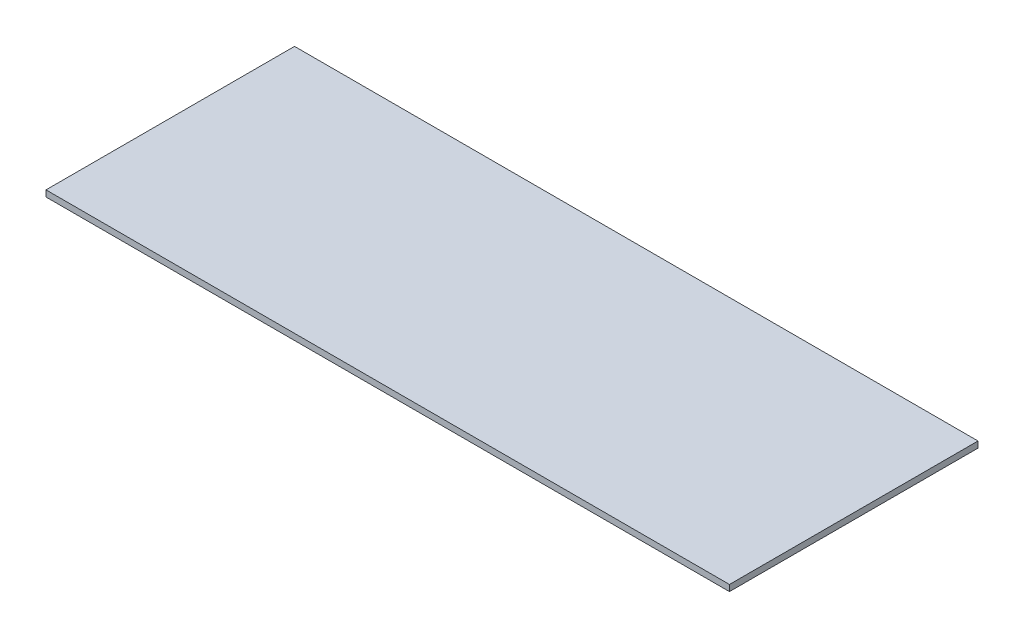
SolidWorks part; units mm, degrees
material "Acrylic (Medium-high impact)"
ref_plane "Front Plane" through (0, 0, 0) normal (0, 0, 1) x (1, 0, 0)
ref_plane "Top Plane" through (0, 0, 0) normal (0, 1, 0) x (1, 0, 0)
ref_plane "Right Plane" through (0, 0, 0) normal (1, 0, 0) x (0, 0, -1)
sketch "Sketch1" plane through (0, 0, 0) normal (0, 1, 0) x (1, 0, 0)
  line L1 (-372.6379, 124.9095) -> (325.8621, 124.9095)
  line L2 (-372.6379, 124.9095) -> (-372.6379, -129.0905)
  line L3 (-372.6379, -129.0905) -> (325.8621, -129.0905)
  line L4 (325.8621, 124.9095) -> (325.8621, -129.0905)
  line L5 (-372.6379, 124.9095) -> (325.8621, -129.0905) construction
  line L6 (-372.6379, -129.0905) -> (325.8621, 124.9095) construction
  point P4 (-23.3879, -2.0905)
  dimension "D1" = 254
  dimension "D2" = 698.5
extrude "Baseplate" add sketch "Sketch1" along normal blind 6.35
sketch "Battery Adaptors" plane through (0, 6.35, 0) normal (0, 1, 0) x (1, 0, 0)
  line L0 (238.575, -103.6905) -> (320.7821, -103.6905) construction
  line L1 (238.575, -103.6905) -> (238.575, -5.2655) construction
  line L2 (238.575, -5.2655) -> (320.7821, -5.2655) construction
  line L3 (320.7821, -103.6905) -> (320.7821, -5.2655) construction
  line L6 (-372.6379, -129.0905) -> (325.8621, -129.0905) construction
  line L7 (325.8621, -129.0905) -> (325.8621, 124.9095) construction
  line L8 (151.2879, -103.6905) -> (233.495, -103.6905) construction
  line L9 (151.2879, -103.6905) -> (151.2879, -5.2655) construction
  line L10 (151.2879, -5.2655) -> (233.495, -5.2655) construction
  line L11 (233.495, -103.6905) -> (233.495, -5.2655) construction
  point P0 (245.525, -10.6655)
  point P5 (313.8321, -10.6655)
  point P6 (299.4721, -98.2905)
  point P7 (259.885, -98.2905)
  point P8 (0, 0)
  point P9 (0, 0)
  point P14 (158.2379, -10.6655)
  point P19 (226.545, -10.6655)
  point P20 (212.185, -98.2905)
  point P21 (172.5979, -98.2905)
  point P22 (0, 0)
  point P23 (0, 0)
  point P24 (0, 0)
  point P25 (0, 0)
  dimension "D1" = 98.425
  dimension "D2" = 82.2071
  dimension "D3" = 5.4
  dimension "D4" = 5.4
  dimension "D5" = 6.95
  dimension "D6" = 6.95
  dimension "D7" = 21.31
  dimension "D8" = 21.31
  dimension "D9" = 25.4
  dimension "D10" = 5.08
  dimension "D11" = 98.425
  dimension "D12" = 82.2071
  dimension "D13" = 6.95
  dimension "D14" = 6.95
  dimension "D15" = 21.31
  dimension "D16" = 21.31
  dimension "D17" = 5.08
sketch "Mounting Points" plane through (0, 6.35, 0) normal (0, 1, 0) x (1, 0, 0)
  line L0 (-372.6379, -116.3905) -> (325.8621, -116.3905) construction
  line L1 (-372.6379, 124.9095) -> (-372.6379, -129.0905) construction
  line L2 (325.8621, -129.0905) -> (325.8621, 124.9095) construction
  line L3 (-372.6379, -129.0905) -> (325.8621, -129.0905) construction
  line L4 (-3.4925, 0) -> (3.4925, 0) construction
  line L5 (-372.6379, 116.3905) -> (325.8621, 116.3905) construction
  point P8 (167.1121, -116.3905)
  point P9 (-206.7505, -116.3905)
  point P10 (14.7121, -116.3905)
  point P11 (-36.0879, -116.3905)
  point P12 (77.6312, -116.3905)
  point P13 (-51.9074, -116.3905)
  point P14 (-6.9143, -116.3905)
  point P15 (-180.8282, -116.3905)
  point P20 (-36.0879, 116.3905)
  point P21 (14.7121, 116.3905)
  point P22 (-206.7505, 116.3905)
  point P23 (167.1121, 116.3905)
  dimension "D1" = 12.7
  dimension "D2" = 158.75
  dimension "D3" = 50.8
  dimension "D4" = 152.4
  dimension "D5" = 170.6626
sketch "Orin Nano" plane through (0, 6.35, 0) normal (0, 1, 0) x (1, 0, 0)
  line L1 (-348.0176, 103.7446) -> (-233.7176, 103.7446) construction
  line L2 (-348.0176, 103.7446) -> (-348.0176, 0.8746) construction
  line L3 (-348.0176, 0.8746) -> (-233.7176, 0.8746) construction
  line L4 (-233.7176, 103.7446) -> (-233.7176, 0.8746) construction
  point P4 (-344.2076, 99.9346)
  point P5 (-237.5276, 99.9346)
  point P6 (-237.5276, 4.6846)
  point P7 (-344.2076, 4.6846)
  point P8 (0, 0)
  point P9 (0, 0)
  point P10 (0, 0)
  point P11 (-87.6745, -75.7345)
  point P12 (-94.8883, 12.5628)
  point P13 (0, -93.7912)
  point P14 (-344.2076, 99.9346)
  dimension "D1" = 102.87
  dimension "D2" = 114.3
  dimension "D3" = 3.81
  dimension "D4" = 3.81
  dimension "D5" = 3.81
  dimension "D6" = 3.81
sketch "Air Tank Shadow" plane through (0, 6.35, 0) normal (0, 1, 0) x (1, 0, 0)
  line L1 (-203.2059, 106.6677) -> (-43.4399, 106.6677) construction
  line L2 (-203.2059, 106.6677) -> (-203.2059, -33.0323) construction
  line L3 (-203.2059, -33.0323) -> (-43.4399, -33.0323) construction
  line L4 (-43.4399, 106.6677) -> (-43.4399, -33.0323) construction
  line L5 (-203.2059, 106.6677) -> (-43.4399, -33.0323) construction
  line L6 (-203.2059, -33.0323) -> (-43.4399, 106.6677) construction
  point P4 (-123.3229, 36.8177)
  point P5 (-123.3229, 36.8177)
  dimension "D1" = 159.766
  dimension "D2" = 139.7
